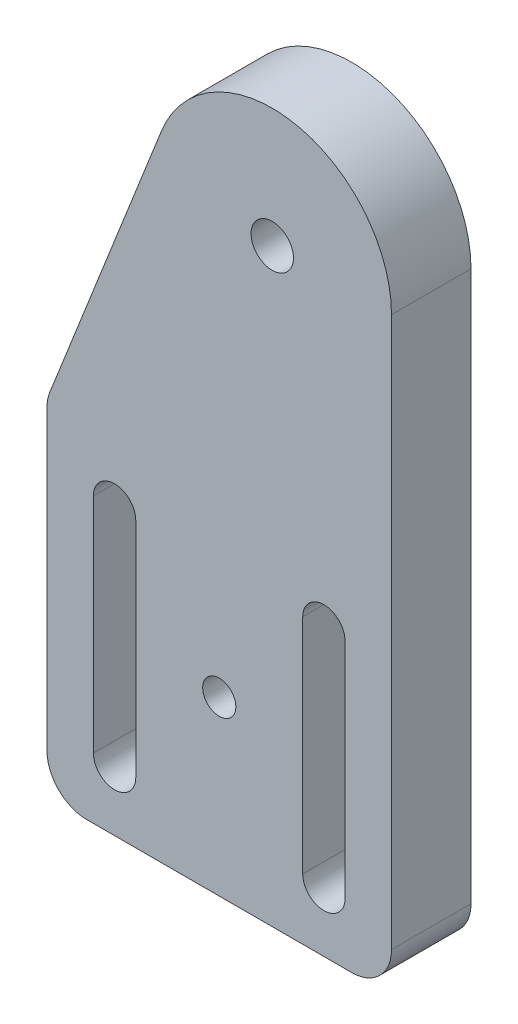
SolidWorks part; units mm, degrees
material "3.1325 (EN-AW 2017A)"
ref_plane "正面" through (0, 0, 0) normal (0, 0, 1) x (1, 0, 0)
ref_plane "平面" through (0, 0, 0) normal (0, 1, 0) x (1, 0, 0)
ref_plane "右側面" through (0, 0, 0) normal (1, 0, 0) x (0, 0, -1)
sketch "ｽｹｯﾁ1" plane through (0, 0, 0) normal (0, 0, 1) x (1, 0, 0)
  line L0 (13, -18.5) -> (13, -44.5)
  line L1 (13, -44.5) -> (-13, -44.5)
  line L2 (-13, -44.5) -> (-13, -18.5)
  line L3 (-13, -18.5) -> (-4.3686, 3.3117)
  line L4 (13, -18.5) -> (13, 0)
  line L5 (-7.9, -23.1) -> (-7.9, -39.9) construction
  line L6 (-6.3, -23.1) -> (-6.3, -39.9)
  line L7 (-13, -18.5) -> (13, -18.5) construction
  line L8 (0, -44.5) -> (0, -18.5) construction
  line L9 (-9.5, -23.1) -> (-9.5, -39.9)
  line L10 (7.9, -23.1) -> (7.9, -39.9) construction
  line L11 (9.5, -23.1) -> (9.5, -39.9)
  line L12 (6.3, -23.1) -> (6.3, -39.9)
  circle A0 centre (4, 0) radius 9 construction
  arc A1 (-4.3686, 3.3117) -> (13, 0) centre (4, 0) cw
  arc A2 (-6.3, -23.1) -> (-9.5, -23.1) centre (-7.9, -23.1) ccw
  arc A3 (-9.5, -39.9) -> (-6.3, -39.9) centre (-7.9, -39.9) ccw
  arc A4 (9.5, -23.1) -> (6.3, -23.1) centre (7.9, -23.1) ccw
  arc A5 (6.3, -39.9) -> (9.5, -39.9) centre (7.9, -39.9) ccw
  circle A6 centre (4, 0) radius 3
  point P11 (-7.9, -31.5)
  point P19 (7.9, -31.5)
  point P28 (0, -31.5)
  dimension "D1" = 26
  dimension "D4" = 18.5
  dimension "D5" = 18
  dimension "D7" = 3
  dimension "D8" = 6
  dimension "D2" = 4
  dimension "D3" = 15.8
  dimension "D6" = 3.2
extrude "ﾎﾞｽ - 押し出し1" add sketch "ｽｹｯﾁ1" along normal blind 6 contours L4 A1 L3 L2 L1 L0 | L6 A3 L9 A2 | L12 A5 L11 A4
extrude "ｶｯﾄ - 押し出し1" cut sketch "ｽｹｯﾁ1<4>" along normal blind 3 contours A6
sketch "ｽｹｯﾁ1<4>" plane through (0, 0, 0) normal (0, 0, 1) x (1, 0, 0) same geometry as "ｽｹｯﾁ1"
hole_wizard "M3x0.5 ねじ穴1" positions "3Dｽｹｯﾁ1" profile "ｽｹｯﾁ2" tap size "M3x0.5" standard "JIS" end condition through all
sketch3d "3Dｽｹｯﾁ1"
  point P0 (0, -31.5, 6)
  point P14 (-14.648, 19.0959, 0)
sketch "ｽｹｯﾁ2" plane through (0, -31.5, 6) normal (1, 0, 0) x (0, -1, 0)
  line L0 (0, 0) -> (0, 6)
  line L1 (0, 6) -> (1.25, 6)
  line L2 (1.25, 6) -> (1.25, 0)
  line L5 (1.25, 0) -> (0, 0)
  line L11 (0, -6.35) -> (0, 107.95) construction
  dimension "ねじ山の主要直径" = 2.5
  dimension "次ｻｰﾌｪｽまでのねじ下穴ﾄﾞﾘﾙの深さ" = 6
hole_wizard "M3 すきま穴1" positions "ｽｹｯﾁ3" profile "ｽｹｯﾁ4" hole size "M3" standard "JIS" end condition through all
sketch "ｽｹｯﾁ3" plane through (0, 0, 6) normal (0, 0, 1) x (1, 0, 0)
  point P0 (4, 0)
sketch "ｽｹｯﾁ4" plane through (4, 0, 6) normal (1, 0, 0) x (0, -1, 0)
  line L0 (0, 0) -> (0, 6)
  line L1 (0, 6) -> (1.6, 6)
  line L2 (1.6, 6) -> (1.6, 0)
  line L5 (1.6, 0) -> (0, 0)
  line L11 (0, -6.35) -> (0, 107.95) construction
  dimension "通し穴の直径" = 3.2
  dimension "通し穴の深さ" = 6
fillet "ﾌｨﾚｯﾄ1" radius 3 3 edges at (13, -44.5, 3) (-13, -44.5, 3) (-13, -18.5, 3)
